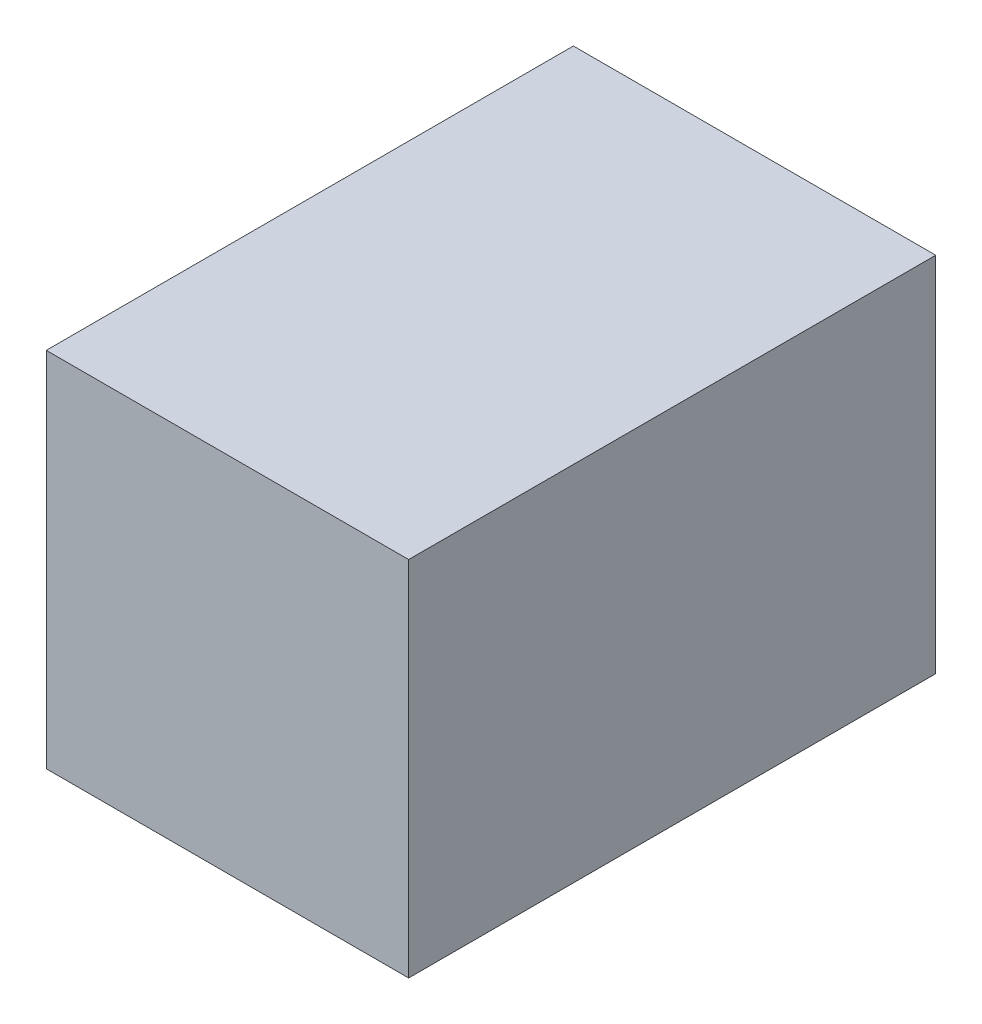
SolidWorks part; units mm, degrees
material "PLA"
ref_plane "Front Plane" through (0, 0, 0) normal (1, 0, 0) x (0, 1, 0)
ref_plane "Top Plane" through (0, 0, 0) normal (0, 0, 1) x (0, 1, 0)
ref_plane "Right Plane" through (0, 0, 0) normal (0, 1, 0) x (-1, 0, 0)
sketch "Sketch1" plane through (0, 0, 0) normal (0, 0, 1) x (0, 1, 0)
  line L1 (-13.75, -13.75) -> (13.75, -13.75)
  line L2 (-13.75, -13.75) -> (-13.75, 13.75)
  line L3 (-13.75, 13.75) -> (13.75, 13.75)
  line L4 (13.75, -13.75) -> (13.75, 13.75)
  line L5 (-13.75, -13.75) -> (13.75, 13.75) construction
  line L6 (-13.75, 13.75) -> (13.75, -13.75) construction
  point P0 (0, 0)
  dimension "D2" = 27.5
extrude "Boss-Extrude1" add sketch "Sketch1" along normal blind 40
equation "\"ball_diameter\"= 3cm"
equation "\"wall_thickness\" = 0.25cm"
equation "\"track_length\" = 25cm"
equation "\"axle\" = 5mm"
equation "\"pillar_width\" = 2.75cm"
equation "\"D2@Sketch1\"=\"pillar_width\""
